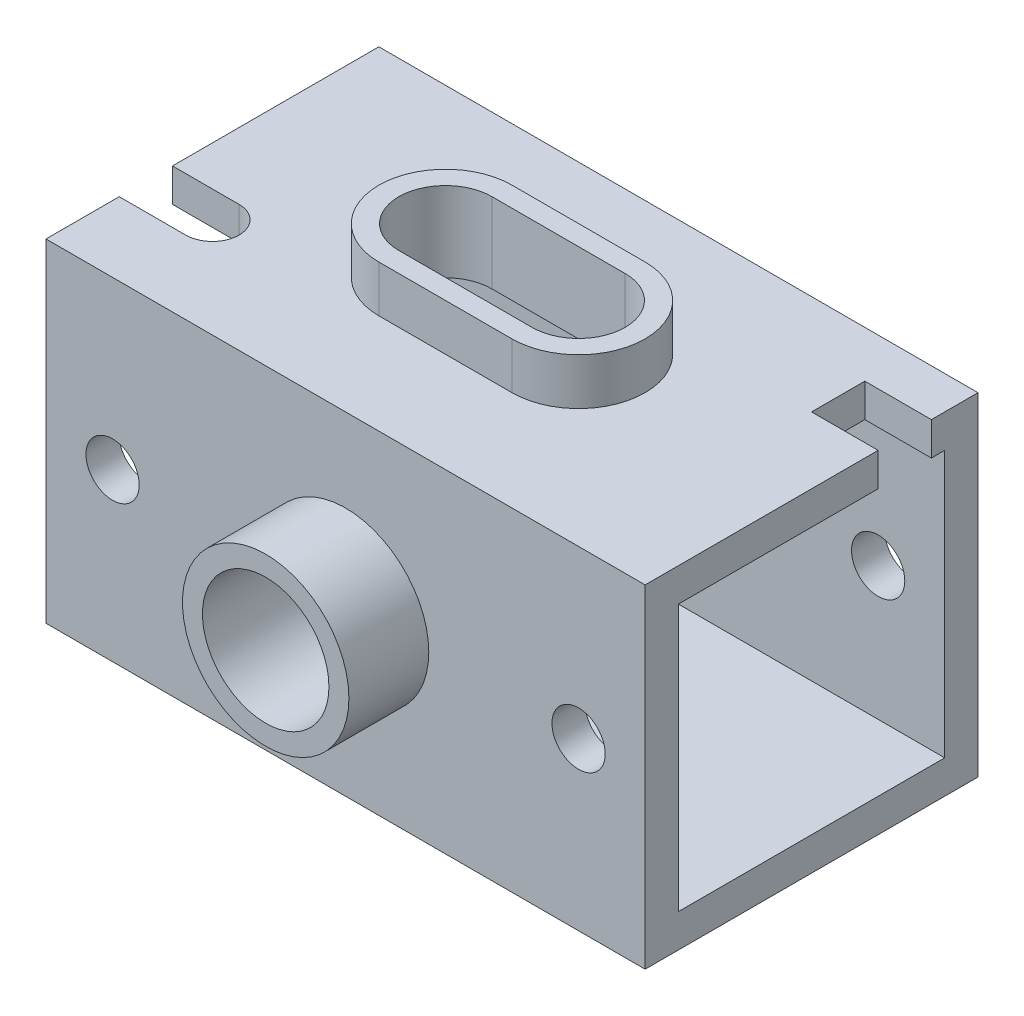
SolidWorks part; units mm, degrees
ref_plane "Front Plane" through (0, 0, 0) normal (0, 0, 1) x (1, 0, 0)
ref_plane "Top Plane" through (0, 0, 0) normal (0, 1, 0) x (1, 0, 0)
ref_plane "Right Plane" through (0, 0, 0) normal (1, 0, 0) x (0, 0, -1)
sketch "Sketch1" plane through (0, 0, 0) normal (0, 0, 1) x (1, 0, 0)
  line L0 (-57.8077, 0) -> (57.1154, 0) construction
  line L1 (-45, -25) -> (45, -25)
  line L2 (-45, -25) -> (-45, 25)
  line L3 (-45, 25) -> (45, 25)
  line L4 (45, -25) -> (45, 25)
  line L5 (-45, -25) -> (45, 25) construction
  line L6 (-45, 25) -> (45, -25) construction
  line L7 (-40, 20) -> (40, 20)
  line L8 (-40, -20) -> (40, -20)
  line L9 (-40, 20) -> (-45, 20)
  line L10 (40, 20) -> (40, -20)
  line L11 (-40, 20) -> (-40, -20)
  line L12 (-40, -20) -> (-45, -20)
  line L13 (40, -20) -> (45, -20)
  line L14 (40, 20) -> (45, 20)
  circle A0 centre (35, 0) radius 4
  circle A1 centre (0, 0) radius 12.5
  circle A2 centre (0, 0) radius 9.5
  circle A3 centre (-35, 0) radius 4
  point P0 (0, 0)
  dimension "D1" = 90
  dimension "D2" = 8
  dimension "D3" = 35
  dimension "D5" = 25
  dimension "D6" = 19
  dimension "D7" = 8
  dimension "D8" = 35
  dimension "D4" = 50
  dimension "D9" = 5
  dimension "D10" = 5
  dimension "D11" = 5
  dimension "D12" = 5
extrude "Boss-Extrude1" add sketch "Sketch1" along normal mid plane 50 contours L1 L4 L3 L2 L11 L7 L10 L8 | L7 L14 L4 L3 L2 L9 region at (0, -22.5, 0) region at (0, 22.5, 0)
extrude "s" add sketch "Sketch1<3>" against normal blind 5 from offset 25 contours L7 L11 L8 L10 A3 A1 A0 region at (-39.1056, 0, 0)
sketch "Sketch1<3>" plane through (0, 0, 0) normal (0, 0, 1) x (1, 0, 0) same geometry as "Sketch1"
extrude "Boss-Extrude3" add sketch "Sketch1<4>" along normal blind 12 and the other way blind 5 from offset 25 contours A1 A2 region at (-12.1464, 0, 0)
sketch "Sketch1<4>" plane through (0, 0, 0) normal (0, 0, 1) x (1, 0, 0) same geometry as "Sketch1"
extrude "Boss-Extrude4" add sketch "Sketch1<5>" against normal blind 5 from offset 25 contours L12 L11 L9 L2 | L14 L10 L13 L4 region at (-42.5, 0, 0) region at (42.5, 0, 0)
sketch "Sketch1<5>" plane through (0, 0, 0) normal (0, 0, 1) x (1, 0, 0) same geometry as "Sketch1"
mirror "Mirror3" about plane through (0, 0, 0) normal (0, 0, 1) of "s", "Boss-Extrude4"
extrude "Boss-Extrude5" add sketch "Sketch1<6>" against normal blind 12 from offset 25 separate body contours A1 A2 region at (-12.1464, 0, 0) offset against normal yes
sketch "Sketch1<6>" plane through (0, 0, 0) normal (0, 0, 1) x (1, 0, 0) same geometry as "Sketch1"
sketch "Sketch2" plane through (0, 25, 0) normal (0, 1, 0) x (1, 0, 0)
  line L0 (-55, -10) -> (-35, -10) construction
  line L1 (-55, -6) -> (-35, -6)
  line L2 (-55, -14) -> (-35, -14)
  line L3 (-10, 0) -> (10, 0) construction
  line L4 (45, 18) -> (35, 18)
  line L5 (45, 18) -> (45, 10)
  line L6 (45, 10) -> (35, 10)
  line L7 (35, 18) -> (35, 10)
  line L8 (-10, 10) -> (10, 10)
  line L9 (-10, -10) -> (10, -10)
  line L10 (-45, -25) -> (45, -25) construction
  line L11 (-45, -25) -> (-45, 25) construction
  line L12 (45, -25) -> (45, 25) construction
  line L13 (-10, 7) -> (10, 7)
  line L14 (-10, -7) -> (10, -7)
  arc A0 (-55, -6) -> (-55, -14) centre (-55, -10) ccw
  arc A1 (-35, -14) -> (-35, -6) centre (-35, -10) ccw
  arc A2 (-10, 10) -> (-10, -10) centre (-10, 0) ccw
  arc A3 (10, -10) -> (10, 10) centre (10, 0) ccw
  arc A4 (10, -7) -> (10, 7) centre (10, 0) ccw
  arc A5 (-10, 7) -> (-10, -7) centre (-10, 0) ccw
  point P2 (-45, -10)
  point P14 (0, 0)
  point P19 (0, 0)
  point P22 (-45, -10)
  line M20 (-45, 25) -> (-45, -25)
  line M22 (45, -25) -> (45, 25)
  dimension "D3" = 4
  dimension "D8" = 10
  dimension "D1" = 8
  dimension "D2" = 10
  dimension "D4" = 20
  dimension "D5" = 15
  dimension "D6" = 10
  dimension "D7" = 20
  dimension "D9" = 3
extrude "Cut-Extrude1" cut sketch "Sketch2" against normal up to next (5 mm away) contours L2 A1 L1 M20 | L4 L7 L6 M22 | L13 A5 L14 A4 region at (-38.3989, 25, 10) region at (40, 25, -14) region at (0, 25, 0)
extrude "Boss-Extrude6" add sketch "Sketch2<3>" along normal blind 7 contours L9 A3 L8 A2 A5 L13 A4 L14 region at (0, 25, -9.5528)
sketch "Sketch2<3>" plane through (0, 25, 0) normal (0, 1, 0) x (1, 0, 0) same geometry as "Sketch2"
